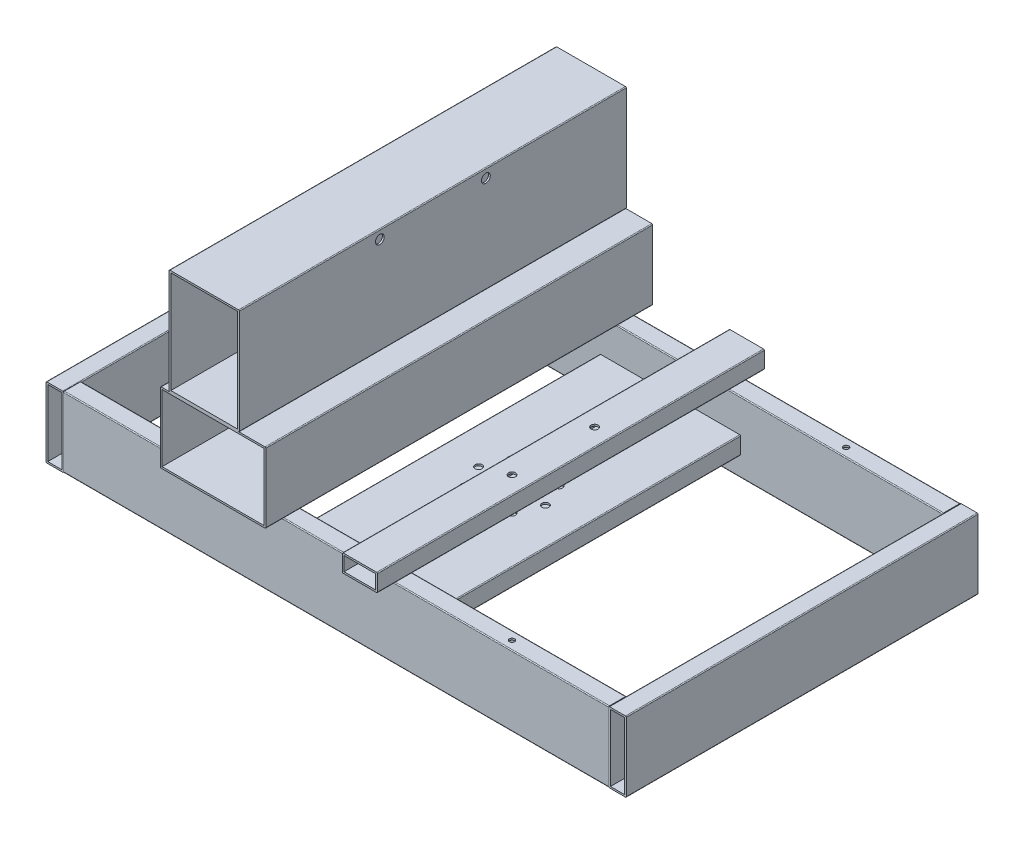
SolidWorks part; units mm, degrees
ref_plane "前视基准面" through (0, 0, 0) normal (0, 0, 1) x (1, 0, 0)
ref_plane "上视基准面" through (0, 0, 0) normal (0, 1, 0) x (1, 0, 0)
ref_plane "右视基准面" through (0, 0, 0) normal (1, 0, 0) x (0, 0, -1)
sketch "草图1" plane through (0, 0, 0) normal (0, 0, 1) x (1, 0, 0)
  line L1 (113.0733, 0) -> (113.0733, 40)
  line L2 (113.0733, 40) -> (103.0733, 40)
  line L3 (103.0733, 40) -> (103.0733, 0)
  line L4 (103.0733, 0) -> (113.0733, 0)
  line L8 (104.0733, 1) -> (104.0733, 39)
  line L9 (104.0733, 39) -> (112.0733, 39)
  line L10 (112.0733, 39) -> (112.0733, 1)
  line L11 (112.0733, 1) -> (104.0733, 1)
sketch "草图9" plane through (0, 0, 0) normal (0, 0, 1) x (1, 0, 0)
  line L9 (223.0733, 80) -> (223.0733, 140)
  line L10 (223.0733, 140) -> (183.0733, 140)
  line L11 (183.0733, 140) -> (183.0733, 80)
  line L12 (183.0733, 80) -> (223.0733, 80)
  line L15 (184.0733, 81) -> (184.0733, 139)
  line L17 (184.0733, 81) -> (222.0733, 81)
  line L18 (184.0733, 139) -> (222.0733, 139)
  line L19 (222.0733, 139) -> (222.0733, 81)
extrude "凸台-拉伸10" add sketch "草图1" along normal blind 100 and the other way blind 100
sketch "草图14" plane through (0, 0, 0) normal (0, 0, 1) x (1, 0, 0)
  line L2 (423.0733, 0) -> (423.0733, 40)
  line L3 (423.0733, 40) -> (433.0733, 40)
  line L4 (433.0733, 40) -> (433.0733, 0)
  line L5 (433.0733, 0) -> (423.0733, 0)
  line L6 (424.0733, 1) -> (424.0733, 39)
  line L7 (424.0733, 39) -> (432.0733, 39)
  line L8 (432.0733, 39) -> (432.0733, 1)
  line L9 (432.0733, 1) -> (424.0733, 1)
extrude "凸台-拉伸11" add sketch "草图14" along normal blind 100 and the other way blind 100
ref_plane "基准面1" through (268.0733, 0, 0) normal (1, 0, 0) x (0, 0, -1)
sketch "草图15" plane through (268.0733, 0, 0) normal (1, 0, 0) x (0, 0, -1)
  line L0 (-100, 40) -> (-90, 40)
  line L1 (-100, 40) -> (-100, 0)
  line L2 (-100, 0) -> (-90, 0)
  line L3 (-90, 40) -> (-90, 0)
  line L4 (-100, 40) -> (-90, 0) construction
  line L5 (-100, 0) -> (-90, 40) construction
  line L6 (-99, 39) -> (-91, 39)
  line L7 (-99, 39) -> (-99, 1)
  line L8 (-99, 1) -> (-91, 1)
  line L9 (-91, 39) -> (-91, 1)
  line L10 (-99, 39) -> (-91, 1) construction
  line L11 (-99, 1) -> (-91, 39) construction
  line L26 (90, 40) -> (100, 40)
  line L27 (90, 40) -> (90, 0)
  line L32 (90, 0) -> (100, 0)
  line L33 (100, 40) -> (100, 0)
  line L34 (90, 40) -> (100, 0) construction
  line L35 (90, 0) -> (100, 40) construction
  line L36 (91, 39) -> (99, 39)
  line L37 (91, 39) -> (91, 1)
  line L38 (91, 1) -> (99, 1)
  line L39 (99, 39) -> (99, 1)
  line L40 (91, 39) -> (99, 1) construction
  line L41 (91, 1) -> (99, 39) construction
  point P4 (-95, 20)
  point P5 (-95, 20)
  point P15 (95, 20)
  point P16 (95, 20)
extrude "凸台-拉伸12" add sketch "草图15" along normal blind 154.999 and the other way blind 154.999
fillet "圆角1" radius 0.5 4 edges at (103.0733, 0, 0) (113.0733, 0, 0) (103.0733, 40, 0) (113.0733, 40, 0)
fillet "圆角2" radius 0.5 4 edges at (433.0733, 0, 0) (433.0733, 40, 0) (423.0733, 0, 0) (423.0733, 40, 0)
fillet "圆角3" radius 0.5 4 edges at (268.0733, 0, 90) (268.0733, 0, 100) (268.0733, 40, 90) (268.0733, 40, 100)
fillet "圆角4" radius 0.5 4 edges at (268.0733, 0, -90) (268.0733, 0, -100) (268.0733, 40, -90) (268.0733, 40, -100)
sketch "草图16" plane through (0, 0, 0) normal (0, 0, 1) x (1, 0, 0)
  line L25 (228.0733, 21) -> (228.0733, 11)
  line L26 (308.0733, 21) -> (308.0733, 11)
  line L27 (228.0733, 11) -> (308.0733, 11)
  line L29 (229.0733, 20) -> (307.0733, 20)
  line L32 (229.0733, 20) -> (229.0733, 12)
  line L33 (307.0733, 20) -> (307.0733, 12)
  line L34 (307.0733, 12) -> (229.0733, 12)
  line L35 (308.0733, 21) -> (228.0733, 21)
extrude "凸台-拉伸14" add sketch "草图16" along normal blind 90 and the other way blind 90
sketch "草图17" plane through (0, 21, 0) normal (0, 1, 0) x (1, 0, 0)
  circle A1 centre (268.0733, 19) radius 2
  circle A2 centre (281.5083, 13.435) radius 2
  circle A3 centre (287.0733, 0) radius 2
  circle A4 centre (281.5083, -13.435) radius 2
  circle A5 centre (268.0733, -19) radius 2
  circle A6 centre (254.6383, -13.435) radius 2
  circle A7 centre (249.0733, 0) radius 2
  circle A8 centre (254.6383, 13.435) radius 2
extrude "切除-拉伸1" cut sketch "草图17" against normal blind 10
fillet "圆角5" radius 0.5 4 edges at (228.0733, 11, 0) (228.0733, 21, 0) (308.0733, 11, 0) (308.0733, 21, 0)
sketch "草图19" plane through (0, 0, 0) normal (0, 0, 1) x (1, 0, 0)
  line L2 (281.5733, 40) -> (281.5733, 50)
  line L3 (281.5733, 50) -> (301.5733, 50)
  line L4 (301.5733, 50) -> (301.5733, 40)
  line L5 (301.5733, 40) -> (281.5733, 40)
  line L6 (282.5733, 41) -> (282.5733, 49)
  line L7 (282.5733, 49) -> (300.5733, 49)
  line L8 (300.5733, 49) -> (300.5733, 41)
  line L9 (300.5733, 41) -> (282.5733, 41)
extrude "凸台-拉伸16" add sketch "草图19" along normal blind 110 and the other way blind 110 separate body
fillet "圆角6" radius 0.5 4 edges at (281.5733, 40, 0) (281.5733, 50, 0) (301.5733, 40, 0) (301.5733, 50, 0)
sketch "草图20" plane through (0, 50, 0) normal (0, 1, 0) x (1, 0, 0)
  circle A0 centre (291.5733, 23.5) radius 2
  circle A1 centre (291.5733, -23.5) radius 2
extrude "切除-拉伸2" cut sketch "草图20" against normal blind 10
extrude "凸台-拉伸17" add sketch "草图9" along normal blind 110 and the other way blind 110
fillet "圆角7" radius 0.5 4 edges at (183.0733, 140, 0) (183.0733, 80, 0) (223.0733, 80, 0) (223.0733, 140, 0)
sketch "草图22" plane through (183.0733, 0, 0) normal (-1, 0, 0) x (0, 0, 1)
  circle A0 centre (-30.15, 135) radius 2.5
  circle A1 centre (30.15, 135) radius 2.5
extrude "切除-拉伸3" cut sketch "草图22" against normal blind 40
sketch "草图23" plane through (0, 0, 0) normal (0, 0, 1) x (1, 0, 0)
  line L1 (223.0733, 80) -> (238.0733, 80)
  line L2 (238.0733, 80) -> (238.0733, 40)
  line L3 (238.0733, 40) -> (178.0733, 40)
  line L4 (178.0733, 40) -> (178.0733, 80)
  line L5 (178.0733, 80) -> (223.0733, 80)
  line L6 (223.0733, 79) -> (237.0733, 79)
  line L7 (237.0733, 79) -> (237.0733, 41)
  line L8 (237.0733, 41) -> (179.0733, 41)
  line L9 (179.0733, 41) -> (179.0733, 79)
  line L10 (179.0733, 79) -> (223.0733, 79)
extrude "凸台-拉伸18" add sketch "草图23" along normal blind 110 and the other way blind 110
fillet "圆角8" radius 0.5 4 edges at (178.0733, 40, 0) (178.0733, 80, 0) (238.0733, 40, 0) (238.0733, 80, 0)
sketch "草图24" plane through (0, 40, 0) normal (0, 1, 0) x (1, 0, 0)
  circle A0 centre (173.0733, 95) radius 1.5
  circle A1 centre (363.0733, 95) radius 1.5
  circle A2 centre (363.0733, -95) radius 1.5
  circle A3 centre (173.0733, -95) radius 1.5
extrude "切除-拉伸4" cut sketch "草图24" against normal blind 40
